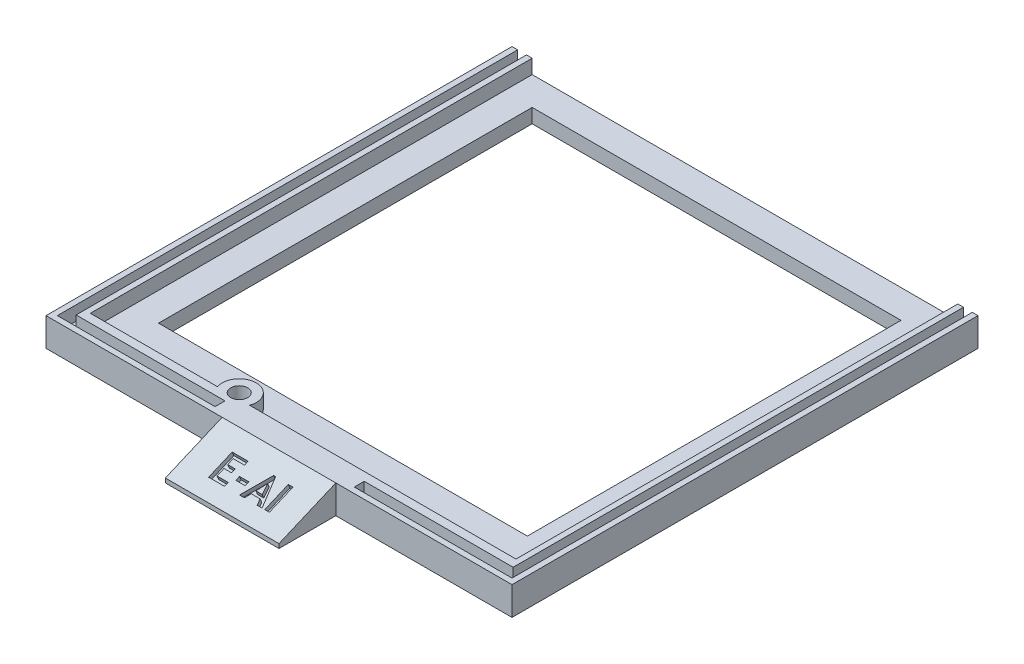
SolidWorks part; units mm, degrees
ref_plane "Front Plane" through (0, 0, 0) normal (0, 0, 1) x (1, 0, 0)
ref_plane "Top Plane" through (0, 0, 0) normal (0, 1, 0) x (1, 0, 0)
ref_plane "Right Plane" through (0, 0, 0) normal (1, 0, 0) x (0, 0, -1)
sketch "Sketch1" plane through (0, 0, 0) normal (0, 1, 0) x (1, 0, 0)
  line L1 (-82, 82) -> (82, 82)
  line L2 (-82, 82) -> (-82, -82)
  line L3 (-82, -82) -> (82, -82)
  line L4 (82, 82) -> (82, -82)
  line L5 (-82, 82) -> (82, -82) construction
  line L6 (-82, -82) -> (82, 82) construction
  point P0 (0, 0)
  dimension "D1" = 164
  dimension "D2" = 164
extrude "Boss-Extrude1" add sketch "Sketch1" along normal blind 5
sketch "Sketch2" plane through (0, 5, 0) normal (0, 1, 0) x (1, 0, 0)
  line L0 (-80, 80) -> (-80, 82)
  line L1 (-82, 82) -> (82, 82)
  line L2 (-82, 82) -> (-82, -82)
  line L3 (-82, -82) -> (-24.5, -82)
  line L4 (82, 82) -> (82, -82)
  line L5 (-82, 82) -> (82, -82) construction
  line L6 (-82, -82) -> (82, 82) construction
  line L8 (-80, 80) -> (-80, -80)
  line L9 (-80, -80) -> (-24.5, -80)
  line L10 (80, 80) -> (80, -80)
  line L11 (-80, 80) -> (80, -80) construction
  line L12 (-80, -80) -> (80, 80) construction
  line L13 (80, 80) -> (80, 82)
  line L14 (-24.5, -78.25) -> (24.5, -78.25) construction
  line L15 (-76.9, 82) -> (-76.9, -76.5)
  line L16 (-76.9, -76.5) -> (-24.5, -76.5)
  line L17 (76.9, -76.5) -> (76.9, 82)
  line L18 (-74.9, 82) -> (-74.9, -74.5)
  line L19 (-74.9, -74.5) -> (74.9, -74.5)
  line L20 (74.9, -74.5) -> (74.9, 82)
  line L21 (-24.5, -82) -> (24.5, -82)
  line L23 (-24.5, -82) -> (-24.5, -74.5)
  line L24 (24.5, -82) -> (24.5, -74.5)
  line L25 (0, -78.25) -> (0, -74.5) construction
  line L26 (24.5, -82) -> (82, -82)
  line L27 (24.5, -80) -> (80, -80)
  line L28 (-82, 82) -> (82, 82)
  line L29 (24.5, -76.5) -> (76.9, -76.5)
  point P0 (0, 0)
  point P7 (0, 0)
  line M17 (82, -82) -> (82, 82)
  line M18 (82, 82) -> (-82, 82)
  line M19 (-82, 82) -> (-82, -82)
  line M20 (-82, -82) -> (82, -82)
  dimension "D1" = 2
  dimension "D2" = 2
  dimension "D3" = 3.1
  dimension "D4" = 3.1
  dimension "D5" = 3.5
  dimension "D6" = 2
  dimension "D7" = 2
  dimension "D8" = 2
  dimension "D11" = 49
  dimension "D12" = 2
extrude "Boss-Extrude2" add sketch "Sketch2" along normal blind 5 contours L23 L9 L8 L0 M20 M18 M19 | L16 L23 L19 L18 L1 L15 | L24 L29 L17 L20 L19 M18 | L27 L24 L13 L10 M20 M17 M18 | L24 L19 M20 | L23 L3 L19 region at (-81.7379, 5, 0) region at (-75.9, 5, -80.3306) region at (0, 5, 78.25) region at (75.9, 5, -80.3306) region at (26.2379, 5, 81)
sketch "Sketch3" plane through (0, 5, 0) normal (0, 1, 0) x (1, 0, 0)
  line L0 (-24.5, -71.5) -> (-24.5, -76.5) construction
  line L1 (-27.8166, -76.5) -> (-24.5, -76.5)
  line L2 (-76.9, -76.5) -> (-24.5, -76.5) construction
  line L3 (-24.5, -76.5) -> (-24.5, -77.5)
  circle A0 centre (-24.5, -71.5) radius 3
  arc A1 (-24.5, -77.5) -> (-27.8166, -76.5) centre (-24.5, -71.5) ccw
  dimension "D1" = 6
  dimension "D3" = 12
  dimension "D4" = 5
extrude "Boss-Extrude3" add sketch "Sketch3" along normal blind 5
sketch "Sketch5" plane through (0, 5, 0) normal (0, 1, 0) x (1, 0, 0)
  line L0 (-64.9, 72) -> (64.9, 72)
  line L1 (64.9, 72) -> (64.9, -59.5)
  line L2 (64.9, -59.5) -> (-64.9, -59.5)
  line L3 (-64.9, -59.5) -> (-64.9, 72)
  line L4 (-74.9, 82) -> (-74.9, -74.5) construction
  line L5 (74.9, -74.5) -> (74.9, 82) construction
  line L6 (74.9, 82) -> (-74.9, 82) construction
  line L7 (-74.9, -74.5) -> (-29.6962, -74.5) construction
  dimension "D1" = 10
  dimension "D2" = 10
  dimension "D3" = 10
  dimension "D4" = 15
extrude "Cut-Extrude1" cut sketch "Sketch5" against normal through all
chamfer "Chamfer2" distance 6 angle 45 2 edges at (-52.2981, 5, 74.5) (27.7981, 5, 74.5)
sketch "Sketch6" plane through (0, 0, 0) normal (1, 0, 0) x (0, 0, -1)
  line L4 (-82, 0) -> (-82, 10)
  line L6 (-102, 0) -> (-82, 0)
  line L7 (-82, 10) -> (-102, 1.5)
  line L8 (-102, 1.5) -> (-102, 0)
  dimension "D1" = 20
  dimension "D2" = 1.5
extrude "Boss-Extrude4" add sketch "Sketch6" along normal mid plane 40
sketch "Sketch7" plane through (0, -16.9382, 145.384) normal (0, -0.9203, -0.3911) x (1, 0, 0)
  line L0 (-20, -53.1396) -> (20, -53.1396) construction
  line L4 (-20, -68.8709) -> (-20, -47.1396) construction
  line L5 (20, -68.8709) -> (20, -47.1396) construction
  line L6 (20, -47.1396) -> (-20, -47.1396) construction
  text T0 "<b>E-AI</b>" font "Trebuchet MS" height 9
  dimension "D1" = 6
extrude "Cut-Extrude3" cut sketch "Sketch7" along normal blind 1.5
